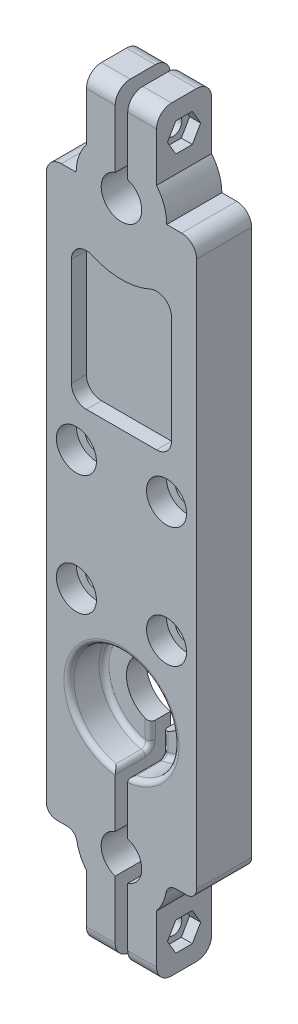
SolidWorks part; units mm, degrees
material "ABS"
ref_plane "Front Plane" through (0, 0, 0) normal (0, 0, 1) x (1, 0, 0)
ref_plane "Top Plane" through (0, 0, 0) normal (0, 1, 0) x (1, 0, 0)
ref_plane "Right Plane" through (0, 0, 0) normal (1, 0, 0) x (0, 0, -1)
sketch "Sketch2" plane through (0, 0, 0) normal (0, 0, 1) x (1, 0, 0)
  line L1 (-15, -17) -> (15, -17)
  line L2 (-15, -17) -> (-15, 17)
  line L3 (-15, 17) -> (15, 17)
  line L4 (15, -17) -> (15, 17)
  line L5 (-15, -17) -> (15, 17) construction
  line L6 (-15, 17) -> (15, -17) construction
  line L7 (-9, -12) -> (9, -12) construction
  line L8 (-9, -12) -> (-9, 12) construction
  line L9 (-9, 12) -> (9, 12) construction
  line L10 (9, -12) -> (9, 12) construction
  line L11 (-9, -12) -> (9, 12) construction
  line L12 (-9, 12) -> (9, -12) construction
  point P0 (0, 0)
  point P6 (0, 0)
  dimension "D1" = 34
  dimension "D2" = 30
  dimension "D3" = 5
  dimension "D4" = 6
extrude "Boss-Extrude1" add sketch "Sketch2" along normal blind 11 contours L3 L4 L1 L2
hole_wizard "CBORE for M4 SHCS1" positions "Sketch3" profile "Sketch4" counterbore size "M4" standard "ANSI Metric" end condition through all
sketch "Sketch3" plane through (0, 0, 11) normal (0, 0, 1) x (1, 0, 0)
  point P0 (-9, 12)
  point P3 (9, 12)
  point P6 (-9, -12)
  point P9 (9, -12)
sketch "Sketch4" plane through (-9, 12, 11) normal (1, 0, 0) x (0, -1, 0)
  line L0 (0, 0) -> (0, 11)
  line L1 (0, 11) -> (2.25, 11)
  line L3 (2.25, 11) -> (2.25, 4)
  line L4 (2.25, 4) -> (4, 4)
  line L5 (4, 4) -> (4, 0)
  line L7 (4, 0) -> (0, 0)
  line L11 (0, -6.35) -> (0, 107.95) construction
  dimension "Thru Hole Dia." = 4.5
  dimension "Thru Hole Depth" = 11
  dimension "C'Bore Dia." = 8
  dimension "C'Bore Depth" = 4
sketch "Sketch6" plane through (0, 0, 0) normal (0, 0, 1) x (1, 0, 0)
  line L0 (15, -17) -> (15, 17) construction
  line L1 (-15, -17) -> (15, -17)
  line L2 (-15, -17) -> (-15, -72.5)
  line L3 (-15, -72.5) -> (15, -72.5)
  line L4 (15, -17) -> (15, -72.5)
  line L5 (15, -17) -> (15, 17) construction
  line L6 (-15, 17) -> (15, 17)
  line L7 (-15, 17) -> (-15, 78.5)
  line L8 (-15, 78.5) -> (15, 78.5)
  line L9 (15, 17) -> (15, 78.5)
  circle A0 centre (0, -29) radius 10.5
  circle A1 centre (0, -54) radius 4.05
  circle A2 centre (0, -29) radius 10 construction
  circle A3 centre (0, -54) radius 4.05 construction
  circle A4 centre (0, 60) radius 4.05
  point P25 (0, 0)
  dimension "D1" = 21
  dimension "D3" = 8.1
  dimension "D5" = 18.5
  dimension "D2" = 60
  dimension "D4" = 55.5
extrude "Boss-Extrude2" add sketch "Sketch6" along normal up to surface (11 mm away) up to face at (-5, 12, 11)
sketch "Sketch8" plane through (0, 0, 0) normal (0, 0, 1) x (1, 0, 0)
  circle A0 centre (0, -29) radius 6
  circle A1 centre (0, -29) radius 10.5
  circle A2 centre (0, -29) radius 10.5 construction
  dimension "D1" = 12
extrude "Boss-Extrude3" add sketch "Sketch8" along normal blind 4 from surface starting at face at (-6.75, 12, 0)
sketch "Sketch7" plane through (0, 0, 11) normal (0, 0, 1) x (1, 0, 0)
  line L0 (-1.25, -72.5) -> (-1.25, 78.5)
  line L5 (-7, -59.7361) -> (-7, -72.5)
  line L6 (-1.25, -72.5) -> (1.25, -72.5)
  line L7 (7, -59.7361) -> (7, -72.5)
  line L8 (-1.25, 78.5) -> (1.25, 78.5)
  line L9 (-15, 78.5) -> (-15, -72.5)
  line L10 (-15, -72.5) -> (15, -72.5)
  line L11 (15, -72.5) -> (15, 78.5)
  line L12 (15, 78.5) -> (-15, 78.5)
  line L13 (-15, 78.5) -> (-15, -72.5)
  line L15 (15, -72.5) -> (15, 78.5)
  line L17 (-9.05, -54) -> (-15, -54)
  line L18 (9.05, -54) -> (15, -54)
  line L19 (1.25, -72.5) -> (1.25, 78.5)
  line L20 (-1.25, -72.5) -> (1.25, 78.5) construction
  line L21 (-7, -59.7361) -> (7, -59.7361) construction
  line L22 (-1.25, 78.5) -> (1.25, -72.5) construction
  line L26 (-15, -72.5) -> (15, -72.5)
  line L31 (-15, 60) -> (-9.05, 60)
  line L32 (9.05, 60) -> (15, 60)
  line L33 (-7, 78.5) -> (-7, 65.7361)
  line L34 (7, 78.5) -> (7, 65.7361)
  line L35 (15, 78.5) -> (-15, 78.5)
  circle A0 centre (0, -29) radius 10.5 construction
  circle A1 centre (0, -29) radius 10.5
  circle A4 centre (0, -54) radius 9.05
  circle A5 centre (0, -54) radius 9.05
  circle A8 centre (0, 60) radius 9.05
  point P1 (0, 3)
  point P36 (7, 65.7361)
  point P37 (1.25, 0)
  line M9 (-15, 78.5) -> (-15, -72.5)
  line M10 (-15, -72.5) -> (15, -72.5)
  line M11 (15, -72.5) -> (15, 78.5)
  circle M13 centre (0, -54) radius 4.05
  circle M14 centre (0, -29) radius 10.5
  line M52 (15, 78.5) -> (-15, 78.5)
  circle M53 centre (0, 60) radius 4.05
  dimension "D3" = 14
  dimension "D4" = 2.5
  dimension "D1" = 0
  dimension "D2" = 5
extrude "Cut-Extrude1" cut sketch "Sketch7" against normal through all and the other way through all contours A5 L17 L13 L5 M10 | A5 L7 L18 M10 M11 | A5 L0 L19 M10 | L19 A5 L0 M13 | A5 L19 L0 M14 | L19 L0 M14 | L0 A5 L19 M13 | A8 L33 L31 M52 M9 | A8 L19 L0 M52 | A8 L32 L34 M11 M52 | L19 A8 L0 M53 region at (0, -67.7605, 11) region at (0, -60.5027, 11) region at (-11.1821, -63.6555, 11) region at (11.1821, -63.6555, 11) region at (0, -47.4973, 11) region at (0, -42.227, 11) region at (-11.1821, 69.6555, 11) region at (0, -29, 11) region at (11.1821, 69.6555, 11) region at (0, 73.7605, 11) region at (0, 66.5027, 11)
fillet "Fillet2" radius 2 4 edges at (15, -54, 5.5) (-15, -54, 5.5) (-9.05, -54, 5.5) (9.05, -54, 5.5)
fillet "Fillet3" radius 1 12 edges at (0, -18.5, 0) (-1.25, -18.5747, 2) (-10.5, -29, 4) (-1.25, -39.4253, 7.5) (0, -18.5, 11) (1.25, -39.4253, 7.5) (10.5, -29, 4) (1.25, -18.5747, 2) (1.25, -37.1468, 4) (1.25, -20.8532, 0) (-1.25, -20.8532, 0) (-1.25, -37.1468, 4)
sketch "Sketch9" plane through (7, 0, 0) normal (1, 0, 0) x (0, 0, -1)
  line L0 (-11, -59.7361) -> (-11, -72.5) construction
  line L1 (-11, -72.5) -> (-11, -59.7361) construction
  line L2 (0, -72.5) -> (-11, -72.5) construction
  line L4 (-2.186, -66.118) -> (-3.843, -63.248)
  line L5 (-3.843, -63.248) -> (-7.157, -63.248)
  line L6 (-7.157, -63.248) -> (-8.814, -66.118)
  line L7 (-8.814, -66.118) -> (-7.157, -68.988)
  line L8 (-7.157, -68.988) -> (-3.843, -68.988)
  line L9 (-3.843, -68.988) -> (-2.186, -66.118)
  circle A0 centre (-5.5, -66.118) radius 1.75
  circle A1 centre (-5.5, -66.118) radius 2.87 construction
  point P7 (-11, -66.118)
  point P11 (-5.5, -72.5)
  dimension "D1" = 3.5
  dimension "D2" = 5.74
extrude "Cut-Extrude2" cut sketch "Sketch9" against normal through all contours A0
extrude "Cut-Extrude3" cut sketch "Sketch9<3>" against normal blind 2.2
sketch "Sketch9<3>" plane through (7, 0, 0) normal (1, 0, 0) x (0, 0, -1) same geometry as "Sketch9"
ref_plane "Plane1" through (0, 3, 0) normal (0, 1, 0) x (1, 0, 0)
mirror "Mirror1" about plane through (0, 3, 0) normal (0, 1, 0) of "Cut-Extrude3", "Cut-Extrude2"
fillet "Fillet4" radius 3 10 edges at (4.125, -72.5, 0) (4.125, -72.5, 11) (-4.125, -72.5, 11) (-4.125, -72.5, 0) (-4.125, 78.5, 11) (4.125, 78.5, 11) (4.125, 78.5, 0) (-4.125, 78.5, 0) (-15, 60, 5.5) (15, 60, 5.5)
ref_plane "Plane2" through (0, 0, 5.5) normal (0, 0, -1) x (-1, 0, 0)
sketch "Sketch11" plane through (0, 0, 0) normal (0, 0, 1) x (1, 0, 0)
  line L40 (-10, 50.1307) -> (-10, 20)
  line L41 (-10, 20) -> (10, 20)
  line L42 (10, 20) -> (10, 50.1307)
  line L43 (-15, -52) -> (-15, 57) construction
  arc A2 (-4.3364, 73.3641) -> (4.3364, 73.3641) centre (0, 60) ccw
  arc A3 (-4.3364, 73.3641) -> (4.3364, 73.3641) centre (0, 60) ccw
  point P2 (0, 20)
  point P3 (10.4283, 19.5447)
  dimension "D2" = 5
  dimension "D3" = 20
  dimension "D1" = 10
extrude "Cut-Extrude4" cut sketch "Sketch11" along normal blind 3 contours A3 L40 L41 L42 region at (0, 33.6511, 0)
mirror "Mirror2" about plane through (0, 0, 5.5) normal (0, 0, -1) of "Cut-Extrude4"
fillet "Fillet5" radius 3 8 edges at (-10, 50.1307, 9.5) (-10, 20, 9.5) (10, 20, 9.5) (10, 50.1307, 9.5) (10, 20, 1.5) (-10, 20, 1.5) (-10, 50.1307, 1.5) (10, 50.1307, 1.5)
